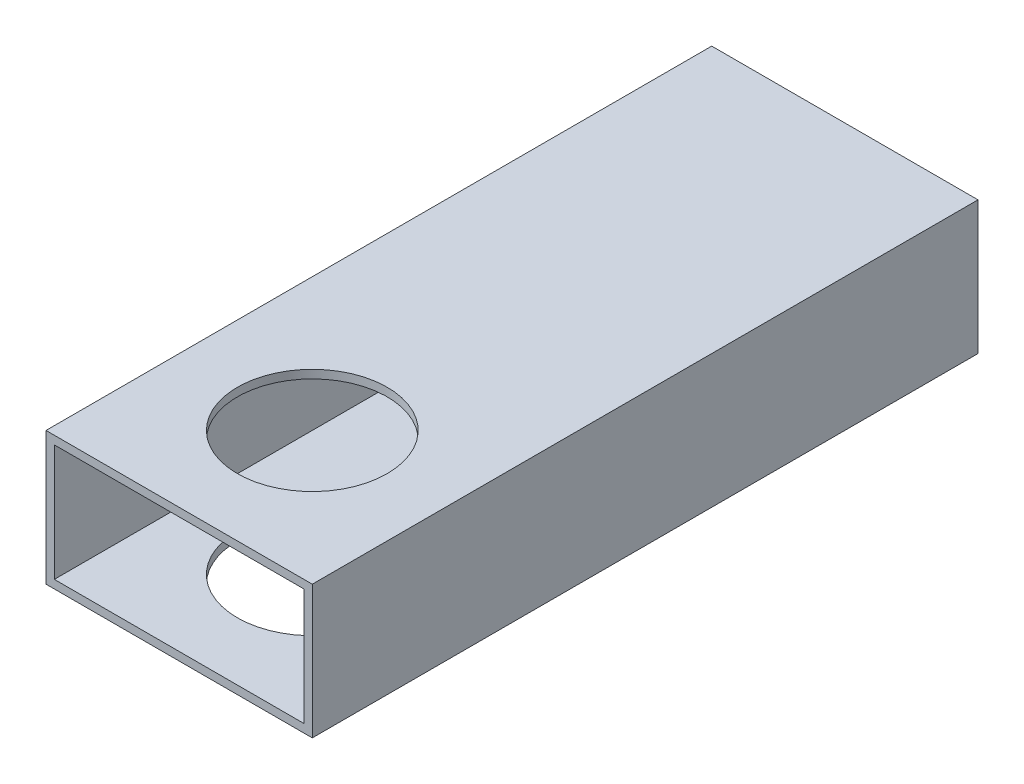
SolidWorks part; units mm, degrees
ref_plane "Front Plane" through (0, 0, 0) normal (0, 0, 1) x (1, 0, 0)
ref_plane "Top Plane" through (0, 0, 0) normal (0, 1, 0) x (1, 0, 0)
ref_plane "Right Plane" through (0, 0, 0) normal (1, 0, 0) x (0, 0, -1)
sketch "Sketch1" plane through (0, 0, 0) normal (0, 0, 1) x (1, 0, 0)
  line L1 (23.8125, -11.1125) -> (-23.8125, -11.1125)
  line L2 (23.8125, -11.1125) -> (23.8125, 11.1125)
  line L3 (23.8125, 11.1125) -> (-23.8125, 11.1125)
  line L4 (-23.8125, -11.1125) -> (-23.8125, 11.1125)
  line L5 (23.8125, -11.1125) -> (-23.8125, 11.1125) construction
  line L6 (23.8125, 11.1125) -> (-23.8125, -11.1125) construction
  line L7 (25.4, -12.7) -> (-25.4, -12.7)
  line L8 (25.4, -12.7) -> (25.4, 12.7)
  line L9 (25.4, 12.7) -> (-25.4, 12.7)
  line L10 (-25.4, -12.7) -> (-25.4, 12.7)
  line L11 (25.4, -12.7) -> (-25.4, 12.7) construction
  line L12 (25.4, 12.7) -> (-25.4, -12.7) construction
  point P0 (0, 0)
  point P6 (0, 0)
  point P11 (12.4812, -13.4339)
  dimension "D1" = 50.8
  dimension "D2" = 25.4
  dimension "D3" = 1.5875
  dimension "D4" = 1.5875
extrude "Boss-Extrude1" add sketch "Sketch1" along normal blind 127
sketch "Sketch2" plane through (0, -12.7, 0) normal (0, -1, 0) x (1, 0, 0)
  line L0 (0, 0) -> (0, 101.6) construction
  line L1 (-25.4, 0) -> (25.4, 0) construction
  circle A0 centre (0, 101.6) radius 14.2875
  dimension "D2" = 28.575
  dimension "D1" = 101.6
extrude "Cut-Extrude1" cut sketch "Sketch2" against normal through all
